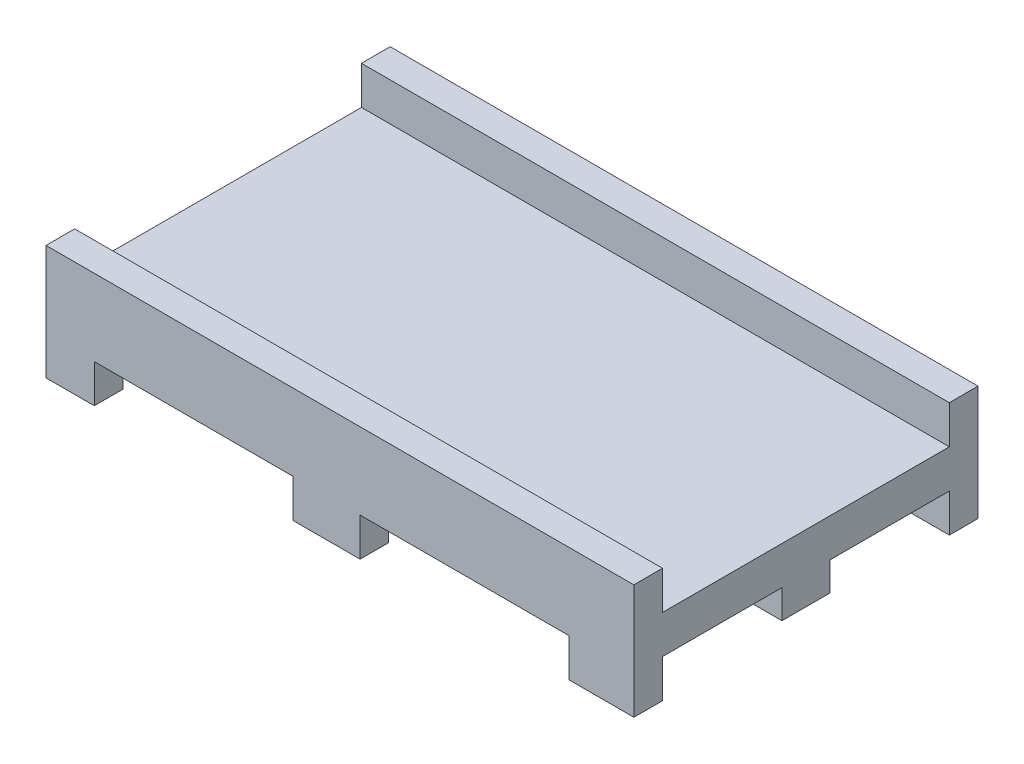
SolidWorks part; units mm, degrees
ref_plane "Front Plane" through (0, 0, 0) normal (0, 0, 1) x (1, 0, 0)
ref_plane "Top Plane" through (0, 0, 0) normal (0, 1, 0) x (1, 0, 0)
ref_plane "Right Plane" through (0, 0, 0) normal (1, 0, 0) x (0, 0, -1)
sketch "Sketch1" plane through (0, 0, 0) normal (0, 1, 0) x (1, 0, 0)
  line L0 (52.07, 0) -> (-52.07, 0) construction
  line L1 (-52.07, -19.05) -> (52.07, -19.05)
  line L2 (-52.07, -19.05) -> (-52.07, 19.05)
  line L3 (-52.07, 19.05) -> (52.07, 19.05)
  line L4 (52.07, -19.05) -> (52.07, 19.05)
  line L5 (-52.07, -19.05) -> (52.07, 19.05) construction
  line L6 (-52.07, 19.05) -> (52.07, -19.05) construction
  line L7 (-52.07, 22.86) -> (52.07, 22.86)
  line L8 (-52.07, 22.86) -> (-52.07, -22.86)
  line L9 (-52.07, -22.86) -> (52.07, -22.86)
  line L10 (52.07, 22.86) -> (52.07, -22.86)
  point P0 (0, 0)
  point P12 (0, 0)
  point P13 (0, 0)
  dimension "D1" = 38.1
  dimension "D2" = 104.14
  dimension "D3" = 3.81
extrude "Boss-Extrude1" add sketch "Sketch1" along normal blind 5.08 contours L10 L1 L8 L9 | L10 L7 L8 L3 region at (0, 0, 20.955) region at (0, 0, -20.955)
sketch "Sketch2" plane through (0, 5.08, 0) normal (0, 1, 0) x (1, 0, 0)
  line L1 (-52.07, 22.86) -> (52.07, 22.86)
  line L2 (-52.07, 22.86) -> (-52.07, -22.86)
  line L3 (-52.07, -22.86) -> (52.07, -22.86)
  line L4 (52.07, 22.86) -> (52.07, -22.86)
extrude "Boss-Extrude2" add sketch "Sketch2" along normal blind 5.08
sketch "Sketch3" plane through (0, 10.16, 0) normal (0, 1, 0) x (1, 0, 0)
  line L0 (52.07, 0) -> (-52.07, 0) construction
  line L1 (-52.07, -19.05) -> (52.07, -19.05)
  line L2 (-52.07, -19.05) -> (-52.07, 19.05)
  line L3 (-52.07, 19.05) -> (52.07, 19.05)
  line L4 (52.07, -19.05) -> (52.07, 19.05)
  line L5 (-52.07, -19.05) -> (52.07, 19.05) construction
  line L6 (-52.07, 19.05) -> (52.07, -19.05) construction
  line L7 (-52.07, 22.86) -> (52.07, 22.86)
  line L8 (-52.07, 22.86) -> (-52.07, -22.86)
  line L9 (-52.07, -22.86) -> (52.07, -22.86)
  line L10 (52.07, 22.86) -> (52.07, -22.86)
  point P0 (0, 0)
  point P11 (0, 0)
  line M9 (-52.07, 22.86) -> (-52.07, -22.86)
  line M10 (-52.07, -22.86) -> (52.07, -22.86)
  line M11 (52.07, -22.86) -> (52.07, 22.86)
  line M12 (52.07, 22.86) -> (-52.07, 22.86)
  dimension "D1" = 38.1
  dimension "D2" = 104.14
  dimension "D3" = 3.81
extrude "Boss-Extrude3" add sketch "Sketch3" along normal blind 5.08 contours L3 M9 M11 M12 | L1 M9 M10 M11 region at (0, 10.16, 20.955) region at (0, 10.16, -20.955)
sketch "Sketch4" plane through (0, 5.08, 0) normal (0, -1, 0) x (1, 0, 0)
  line L0 (52.07, 19.05) -> (52.07, -19.05) construction
  line L1 (-52.07, -3.1877) -> (52.07, -3.1877)
  line L2 (-52.07, -3.1877) -> (-52.07, 3.1877)
  line L3 (-52.07, 3.1877) -> (52.07, 3.1877)
  line L4 (52.07, -3.1877) -> (52.07, 3.1877)
  line L5 (-52.07, -3.1877) -> (52.07, 3.1877) construction
  line L6 (-52.07, 3.1877) -> (52.07, -3.1877) construction
  point P0 (0, 0)
  dimension "D1" = 6.3754
extrude "Boss-Extrude4" add sketch "Sketch4" along normal blind 3.81
sketch "Sketch5" plane through (0, 0, 22.86) normal (0, 0, 1) x (1, 0, 0)
  line L0 (-52.07, 0) -> (52.07, 0) construction
  line L1 (-45.6558, 0) -> (-19.2872, 0)
  line L2 (-45.6558, 0) -> (-45.6558, 5.08)
  line L3 (-45.6558, 5.08) -> (-19.2872, 5.08)
  line L4 (-19.2872, 0) -> (-19.2872, 5.08)
  line L6 (-10.348, 0) -> (17.4085, 0)
  line L7 (-10.348, 0) -> (-10.348, 5.08)
  line L8 (-10.348, 5.08) -> (17.4085, 5.08)
  line L9 (17.4085, 0) -> (17.4085, 5.08)
  line L10 (26.0257, 20.6101) -> (56.3311, 20.6101)
  line L11 (26.0257, 20.6101) -> (26.0257, -5.4351)
  line L12 (26.0257, -5.4351) -> (56.3311, -5.4351)
  line L13 (56.3311, 20.6101) -> (56.3311, -5.4351)
  dimension "D1" = 5.08
  dimension "D2" = 5.08
extrude "Cut-Extrude1" cut sketch "Sketch5" against normal through all both and the other way through all
